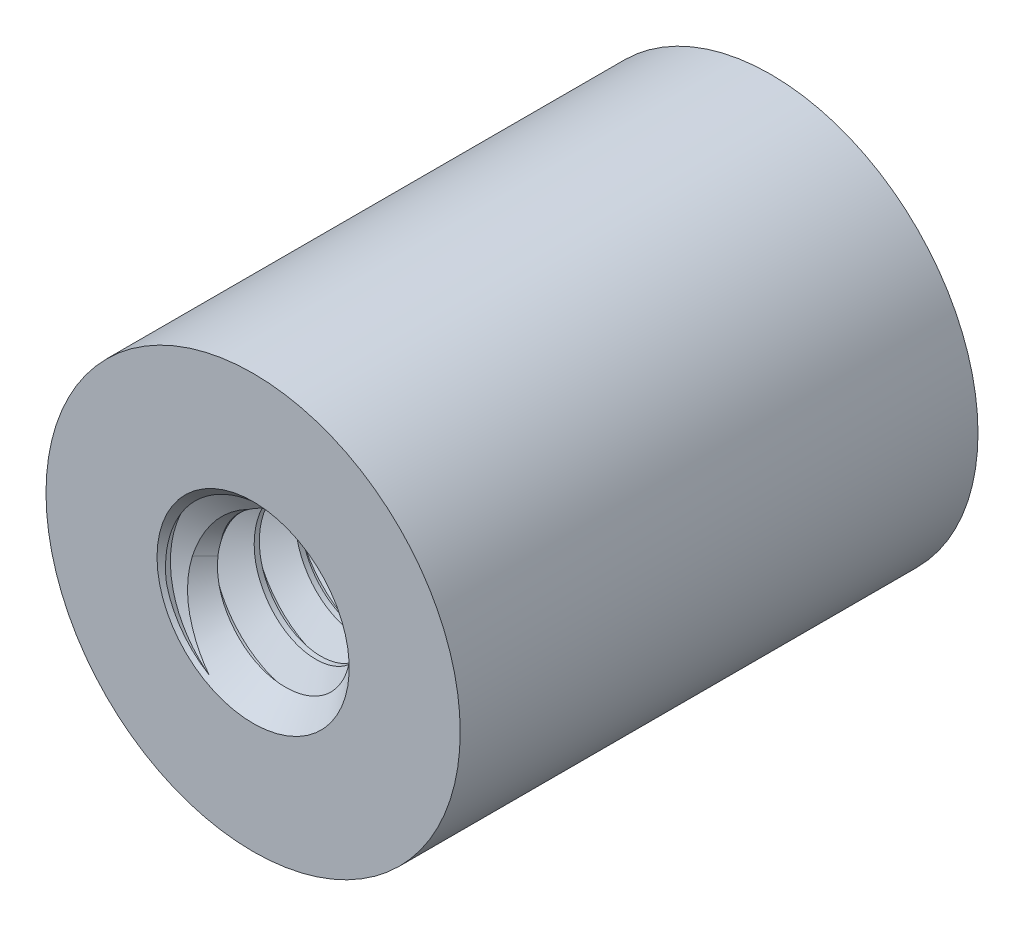
SolidWorks part; units mm, degrees
ref_plane "Front Plane" through (0, 0, 0) normal (0, 0, 1) x (1, 0, 0)
ref_plane "Top Plane" through (0, 0, 0) normal (0, 1, 0) x (1, 0, 0)
ref_plane "Right Plane" through (0, 0, 0) normal (1, 0, 0) x (0, 0, -1)
sketch "Sketch3" plane through (0, 0, 0) normal (1, 0, 0) x (0, 0, -1)
  line L0 (-3.9688, 0) -> (3.9688, 0) construction
  line L1 (0, 3.175) -> (0, -3.175) construction
  line L2 (-3.9688, 1.4224) -> (-3.9688, -1.4224) construction
  point P2 (-7.1437, 0)
  point P3 (7.1437, 0)
  dimension "D1" = 11.1125
  dimension "Length" = 7.9375
  dimension "Min Thread Length" = 11.1125
  dimension "Thread Dia" = 2.8448
  dimension "OD" = 6.35
sketch "Sketch1" plane through (0, 0, 0) normal (0, 0, 1) x (1, 0, 0)
  circle A1 centre (0, 0) radius 1.4224
  circle A2 centre (0, 0) radius 3.175
extrude "Extrude1" add sketch "Sketch1" along normal up to vertex (3.9688 mm away) and the other way up to vertex (3.9688 mm away) up to point (0, 0, 3.9688) other way up to point (0, 0, -3.9688)
sketch "Sketch11" plane through (0, 0, -3.9688) normal (0, 0, -1) x (-1, 0, 0)
  circle A0 centre (0, 0) radius 1.4224 construction
  circle A1 centre (0, 0) radius 1.4224
curve "Helix/Spiral1" pitch 0.635 height 8.5725 radius 1.4224 centre (0, 0, -3.9688) axis (0, 0, 1) start towards (0, 1, 0) parameters "Pitch"=0.635
sketch "Sketch12" plane through (0, 0, 0) normal (1, 0, 0) x (0, 0, -1)
  line L0 (4.5244, 1.4224) -> (3.9688, 1.4224)
  line L1 (4.5244, 1.4224) -> (4.2863, 1.01)
  line L2 (4.2863, 1.01) -> (4.2069, 1.01)
  line L3 (4.2069, 1.01) -> (3.9688, 1.4224)
  line L4 (4.2466, 1.01) -> (4.2466, 1.4224) construction
  line L5 (4.4053, 1.2162) -> (4.0878, 1.2162) construction
  dimension "D1" = 0.0794
  dimension "D2" = 0.3175
  dimension "D3" = 60
sweep "Sweep1" add profiles "Sketch12" path "Helix/Spiral1"
sketch "Sketch6" plane through (0, 0, -3.9688) normal (0, 0, -1) x (-1, 0, 0)
  circle A1 centre (0, 0) radius 3.175
  circle A2 centre (0, 0) radius 3.175
  dimension "D1" = 0
extrude "Extrude2" cut sketch "Sketch6" along normal through all
sketch "Sketch7" plane through (0, 0, -3.9688) normal (0, 0, -1) x (-1, 0, 0)
  circle A2 centre (0, 0) radius 1.4732
  circle A3 centre (0, 0) radius 1.4732
  dimension "D1" = 0.0508
extrude "Extrude3" cut sketch "Sketch7" against normal through all draft 43
mirror "Mirror1" about plane through (0, 0, 0) normal (0, 0, 1) of "Extrude2", "Extrude3"
sketch "Sketch9" [suppressed] plane through (0, 0, 0) normal (1, 0, 0) x (0, 0, -1)
  line L1 (-20.6375, 2.1336) -> (20.6375, 2.1336)
  line L2 (-20.6375, 2.1336) -> (-20.6375, 0)
  line L3 (-20.6375, 0) -> (20.6375, 0)
  line L4 (20.6375, 2.1336) -> (20.6375, 0)
  line L7 (-31.75, 0) -> (31.75, 0) construction
revolve "Revolve" [suppressed] add sketch "Sketch9" angle 360 about L0
sketch "Sketch10" [suppressed] plane through (0, 0, 0) normal (1, 0, 0) x (0, 0, -1)
  line L0 (31.75, 2.0828) -> (20.6375, 2.0828)
  line L1 (-31.75, 2.0828) -> (-20.6375, 2.0828)
  line L2 (20.6375, 2.0828) -> (20.6375, -2.0828)
  line L3 (-31.75, -2.1336) -> (-20.6375, -2.1336)
  line L4 (-20.6375, 2.0828) -> (-20.6375, -2.1336)
  line L5 (20.6375, -2.0828) -> (31.75, -2.0828)
equation "\"D1@Sketch3\" = \"Min Thread Length@Sketch3\""
equation "\"D3@Helix/Spiral1\" = \"Length@Sketch3\"+\"Pitch@Helix/Spiral1\""
equation "\"D1@Sketch12\" = \"Pitch@Helix/Spiral1\"*.125"
equation "\"D2@Sketch12\" = \"Pitch@Helix/Spiral1\"*.5"
